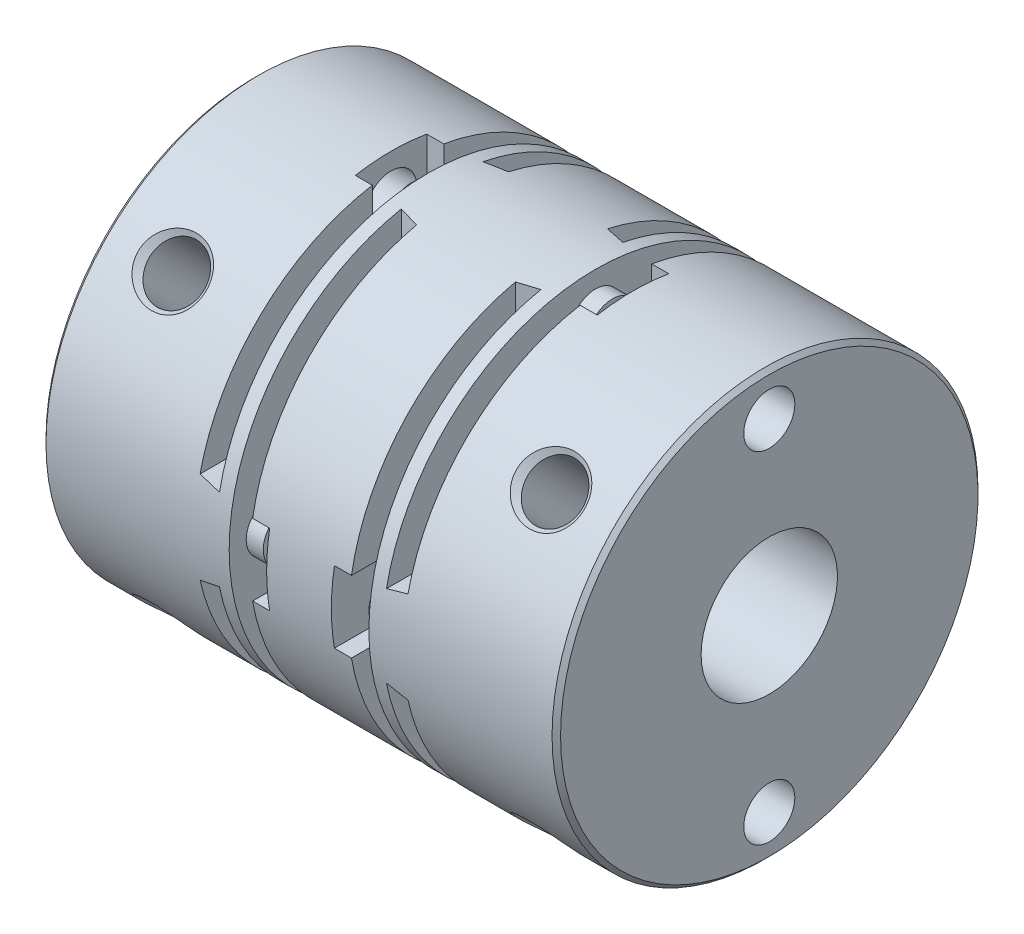
SolidWorks part; units mm, degrees
material "6061 合金"
ref_plane "前视基准面" through (0, 0, 0) normal (0, 0, 1) x (1, 0, 0)
ref_plane "上视基准面" through (0, 0, 0) normal (0, 1, 0) x (1, 0, 0)
ref_plane "右视基准面" through (0, 0, 0) normal (1, 0, 0) x (0, 0, -1)
sketch "草图1" plane through (0, 0, 0) normal (0, 0, 1) x (1, 0, 0)
  line L0 (0, 4) -> (9, 4)
  line L1 (9, 4) -> (9, 7.5)
  line L2 (9, 7.5) -> (10.2, 7.5)
  line L3 (10.2, 7.5) -> (10.2, 6)
  line L4 (10.2, 6) -> (11, 6)
  line L5 (11, 6) -> (11, 7.5)
  line L6 (11, 7.5) -> (12.2, 7.5)
  line L7 (12.2, 7.5) -> (12.2, 5.2)
  line L8 (12.2, 5.2) -> (18, 5.2)
  line L9 (18, 5.2) -> (18, 7.5)
  line L10 (18, 7.5) -> (19.2, 7.5)
  line L11 (19.2, 7.5) -> (19.2, 6)
  line L12 (19.2, 6) -> (20, 6)
  line L13 (20, 6) -> (20, 7.5)
  line L14 (20, 7.5) -> (21.2, 7.5)
  line L15 (21.2, 7.5) -> (21.2, 4)
  line L16 (21.2, 4) -> (30.2, 4)
  line L17 (30.2, 4) -> (30.2, 12.25)
  line L18 (30.2, 12.25) -> (29.95, 12.5)
  line L19 (29.95, 12.5) -> (0.25, 12.5)
  line L20 (0.25, 12.5) -> (0, 12.25)
  line L21 (0, 12.25) -> (0, 4)
  line L22 (30.2, 0) -> (0, 0) construction
revolve "旋转1" add sketch "草图1" angle 360 about L22 reverse direction yes
ref_plane "基准面1" through (4, 0, 0) normal (1, 0, 0) x (0, 0, -1)
sketch "草图2" plane through (4, 0, 0) normal (1, 0, 0) x (0, 0, -1)
  line L0 (-8.8388, 8.8388) -> (-7.4246, 10.253)
  line L1 (-7.4246, 10.253) -> (-7.4246, 9.7171)
  line L2 (-7.4246, 9.7171) -> (1.1462, 1.1462)
  line L3 (1.1462, 1.1462) -> (0, 0)
  line L4 (0, 0) -> (-8.8388, 8.8388)
  line L5 (0, 0) -> (-8.8388, 8.8388) construction
revolve "切除-旋转1" cut sketch "草图2" angle 360 about L5 reverse direction yes
cosmetic thread "装饰螺纹线1" parameters "D1"=8.5, "D2"=4
sketch "草图3" plane through (4, 0, 0) normal (1, 0, 0) x (0, 0, -1)
  line L0 (-8.8388, -8.8388) -> (-10.253, -7.4246)
  line L1 (-10.253, -7.4246) -> (-9.7171, -7.4246)
  line L2 (-9.7171, -7.4246) -> (-1.1462, 1.1462)
  line L3 (-1.1462, 1.1462) -> (0, 0)
  line L4 (0, 0) -> (-8.8388, -8.8388)
  line L5 (0, 0) -> (-8.8388, -8.8388) construction
revolve "切除-旋转2" cut sketch "草图3" angle 360 about L5 reverse direction yes
cosmetic thread "装饰螺纹线2" parameters "D1"=8.5, "D2"=4
ref_plane "基准面2" through (26.2, 0, 0) normal (1, 0, 0) x (0, 0, -1)
sketch "草图4" plane through (26.2, 0, 0) normal (1, 0, 0) x (0, 0, -1)
  line L0 (-8.8388, 8.8388) -> (-7.4246, 10.253)
  line L1 (-7.4246, 10.253) -> (-7.4246, 9.7171)
  line L2 (-7.4246, 9.7171) -> (1.1462, 1.1462)
  line L3 (1.1462, 1.1462) -> (0, 0)
  line L4 (0, 0) -> (-8.8388, 8.8388)
  line L5 (0, 0) -> (-8.8388, 8.8388) construction
revolve "切除-旋转3" cut sketch "草图4" angle 360 about L5 reverse direction yes
cosmetic thread "装饰螺纹线3" parameters "D1"=8.5, "D2"=4
sketch "草图5" plane through (26.2, 0, 0) normal (1, 0, 0) x (0, 0, -1)
  line L0 (-8.8388, -8.8388) -> (-10.253, -7.4246)
  line L1 (-10.253, -7.4246) -> (-9.7171, -7.4246)
  line L2 (-9.7171, -7.4246) -> (-1.1462, 1.1462)
  line L3 (-1.1462, 1.1462) -> (0, 0)
  line L4 (0, 0) -> (-8.8388, -8.8388)
  line L5 (0, 0) -> (-8.8388, -8.8388) construction
revolve "切除-旋转4" cut sketch "草图5" angle 360 about L5 reverse direction yes
cosmetic thread "装饰螺纹线4" parameters "D1"=8.5, "D2"=4
sketch "草图6" plane through (0, 0, 0) normal (0, 0, 1) x (1, 0, 0)
  line L0 (9, 13) -> (9, 2.7)
  line L1 (9, 2.7) -> (10.2, 2.4)
  line L2 (10.2, 2.4) -> (10.2, 12.5)
  line L3 (10.2, 12.5) -> (20, 12.5)
  line L4 (20, 12.5) -> (20, 2.4)
  line L5 (20, 2.4) -> (21.2, 2.7)
  line L6 (21.2, 2.7) -> (21.2, 13)
  line L7 (21.2, 13) -> (9, 13)
extrude "切除-拉伸1" cut sketch "草图6" along normal blind 12.5 and the other way blind 12.5
sketch "草图7" plane through (0, 0, 0) normal (0, 0, 1) x (1, 0, 0)
  line L0 (9, -13) -> (21.2, -13)
  line L1 (21.2, -13) -> (21.2, -2.7)
  line L2 (21.2, -2.7) -> (20, -2.4)
  line L3 (20, -2.4) -> (20, -12.5)
  line L4 (20, -12.5) -> (10.2, -12.5)
  line L5 (10.2, -12.5) -> (10.2, -2.4)
  line L6 (10.2, -2.4) -> (9, -2.7)
  line L7 (9, -2.7) -> (9, -13)
extrude "切除-拉伸2" cut sketch "草图7" along normal blind 12.5 and the other way blind 12.5
sketch "草图8" plane through (0, 0, 0) normal (0, 1, 0) x (1, 0, 0)
  line L0 (11, 13) -> (11, 2.4)
  line L1 (11, 2.4) -> (12.2, 2.7)
  line L2 (12.2, 2.7) -> (12.2, 12.5)
  line L3 (12.2, 12.5) -> (18, 12.5)
  line L4 (18, 12.5) -> (18, 2.7)
  line L5 (18, 2.7) -> (19.2, 2.4)
  line L6 (19.2, 2.4) -> (19.2, 13)
  line L7 (19.2, 13) -> (11, 13)
extrude "切除-拉伸3" cut sketch "草图8" along normal blind 12.5 and the other way blind 12.5
sketch "草图9" plane through (0, 0, 0) normal (0, 1, 0) x (1, 0, 0)
  line L0 (11, -13) -> (19.2, -13)
  line L1 (19.2, -13) -> (19.2, -2.4)
  line L2 (19.2, -2.4) -> (18, -2.7)
  line L3 (18, -2.7) -> (18, -12.5)
  line L4 (18, -12.5) -> (12.2, -12.5)
  line L5 (12.2, -12.5) -> (12.2, -2.7)
  line L6 (12.2, -2.7) -> (11, -2.4)
  line L7 (11, -2.4) -> (11, -13)
extrude "切除-拉伸4" cut sketch "草图9" along normal blind 12.5 and the other way blind 12.5
ref_plane "基准面3" through (18, 0, 0) normal (1, 0, 0) x (0, 0, -1)
sketch "草图10" plane through (18, 0, 0) normal (1, 0, 0) x (0, 0, -1)
  line L0 (-12.5, -2.1) -> (-10, -2.1)
  line L1 (-10, 2.1) -> (-12.5, 2.1)
  line L2 (-12.5, 2.1) -> (-12.5, -2.1)
  arc A0 (-10, -2.1) -> (-10, 2.1) centre (-10, 0) ccw
extrude "切除-拉伸5" cut sketch "草图10" against normal blind 1
sketch "草图11" plane through (18, 0, 0) normal (1, 0, 0) x (0, 0, -1)
  line L0 (10, -2.1) -> (12.5, -2.1)
  line L1 (12.5, -2.1) -> (12.5, 2.1)
  line L2 (12.5, 2.1) -> (10, 2.1)
  arc A0 (10, 2.1) -> (10, -2.1) centre (10, 0) ccw
extrude "切除-拉伸6" cut sketch "草图11" against normal blind 1
ref_plane "基准面4" through (12.2, 0, 0) normal (1, 0, 0) x (0, 0, -1)
sketch "草图12" plane through (12.2, 0, 0) normal (1, 0, 0) x (0, 0, -1)
  line L0 (-12.5, -2.1) -> (-10, -2.1)
  line L1 (-10, 2.1) -> (-12.5, 2.1)
  line L2 (-12.5, 2.1) -> (-12.5, -2.1)
  arc A0 (-10, -2.1) -> (-10, 2.1) centre (-10, 0) ccw
extrude "切除-拉伸7" cut sketch "草图12" along normal blind 1
sketch "草图13" plane through (12.2, 0, 0) normal (1, 0, 0) x (0, 0, -1)
  line L0 (10, -2.1) -> (12.5, -2.1)
  line L1 (12.5, -2.1) -> (12.5, 2.1)
  line L2 (12.5, 2.1) -> (10, 2.1)
  arc A0 (10, 2.1) -> (10, -2.1) centre (10, 0) ccw
extrude "切除-拉伸8" cut sketch "草图13" along normal blind 1
ref_plane "基准面5" through (9, 0, 0) normal (1, 0, 0) x (0, 0, -1)
sketch "草图14" plane through (9, 0, 0) normal (1, 0, 0) x (0, 0, -1)
  line L0 (2.1, 10) -> (2.1, 12.5)
  line L1 (2.1, 12.5) -> (-2.1, 12.5)
  line L2 (-2.1, 12.5) -> (-2.1, 10)
  arc A0 (-2.1, 10) -> (2.1, 10) centre (0, 10) ccw
extrude "切除-拉伸9" cut sketch "草图14" against normal blind 1
sketch "草图15" plane through (9, 0, 0) normal (1, 0, 0) x (0, 0, -1)
  line L0 (-2.1, -10) -> (-2.1, -12.5)
  line L1 (-2.1, -12.5) -> (2.1, -12.5)
  line L2 (2.1, -12.5) -> (2.1, -10)
  arc A0 (2.1, -10) -> (-2.1, -10) centre (0, -10) ccw
extrude "切除-拉伸10" cut sketch "草图15" against normal blind 1
ref_plane "基准面6" through (21.2, 0, 0) normal (1, 0, 0) x (0, 0, -1)
sketch "草图16" plane through (21.2, 0, 0) normal (1, 0, 0) x (0, 0, -1)
  line L0 (2.1, 10) -> (2.1, 12.5)
  line L1 (2.1, 12.5) -> (-2.1, 12.5)
  line L2 (-2.1, 12.5) -> (-2.1, 10)
  arc A0 (-2.1, 10) -> (2.1, 10) centre (0, 10) ccw
extrude "切除-拉伸11" cut sketch "草图16" along normal blind 1
sketch "草图17" plane through (21.2, 0, 0) normal (1, 0, 0) x (0, 0, -1)
  line L0 (-2.1, -10) -> (-2.1, -12.5)
  line L1 (-2.1, -12.5) -> (2.1, -12.5)
  line L2 (2.1, -12.5) -> (2.1, -10)
  arc A0 (2.1, -10) -> (-2.1, -10) centre (0, -10) ccw
extrude "切除-拉伸12" cut sketch "草图17" along normal blind 1
ref_plane "基准面7" through (11, 0, 0) normal (1, 0, 0) x (0, 0, -1)
sketch "草图18" plane through (11, 0, 0) normal (1, 0, 0) x (0, 0, -1)
  circle A0 centre (-10, 0) radius 1.5
extrude "凸台-拉伸1" add sketch "草图18" along normal blind 1
sketch "草图19" plane through (11, 0, 0) normal (1, 0, 0) x (0, 0, -1)
  circle A0 centre (10, 0) radius 1.5
extrude "凸台-拉伸2" add sketch "草图19" along normal blind 1
ref_plane "基准面8" through (10.2, 0, 0) normal (1, 0, 0) x (0, 0, -1)
sketch "草图20" plane through (10.2, 0, 0) normal (1, 0, 0) x (0, 0, -1)
  circle A0 centre (0, 10) radius 1.5
extrude "凸台-拉伸3" add sketch "草图20" against normal blind 1
sketch "草图21" plane through (10.2, 0, 0) normal (1, 0, 0) x (0, 0, -1)
  circle A0 centre (0, -10) radius 1.5
extrude "凸台-拉伸4" add sketch "草图21" against normal blind 1
ref_plane "基准面9" through (19.2, 0, 0) normal (1, 0, 0) x (0, 0, -1)
sketch "草图22" plane through (19.2, 0, 0) normal (1, 0, 0) x (0, 0, -1)
  circle A0 centre (-10, 0) radius 1.5
extrude "凸台-拉伸5" add sketch "草图22" against normal blind 1
sketch "草图23" plane through (19.2, 0, 0) normal (1, 0, 0) x (0, 0, -1)
  circle A0 centre (10, 0) radius 1.5
extrude "凸台-拉伸6" add sketch "草图23" against normal blind 1
ref_plane "基准面10" through (20, 0, 0) normal (1, 0, 0) x (0, 0, -1)
sketch "草图24" plane through (20, 0, 0) normal (1, 0, 0) x (0, 0, -1)
  circle A0 centre (0, 10) radius 1.5
extrude "凸台-拉伸7" add sketch "草图24" along normal blind 1
sketch "草图25" plane through (20, 0, 0) normal (1, 0, 0) x (0, 0, -1)
  circle A0 centre (0, -10) radius 1.5
extrude "凸台-拉伸8" add sketch "草图25" along normal blind 1
hole_wizard "孔1" positions "草图27" profile "草图26" legacy
sketch "草图27" plane through (0, 0, 0) normal (-1, 0, 0) x (0, 0, 1)
  point P0 (0, 10)
sketch "草图26" plane through (0, 10, 0) normal (0, 1, 0) x (0, 0, 1)
  line L0 (0, 0) -> (0, 9)
  line L1 (0, 9) -> (1.5, 9)
  line L2 (1.5, 9) -> (1.5, 0)
  line L3 (1.5, 0) -> (0, 0)
  line L4 (0, 110) -> (0, -10) construction
  dimension "直径" = 3
  dimension "深度" = 9
hole_wizard "孔2" positions "草图29" profile "草图28" legacy
sketch "草图29" plane through (0, 0, 0) normal (-1, 0, 0) x (0, 0, 1)
  point P0 (0, -10)
sketch "草图28" plane through (0, -10, 0) normal (0, 1, 0) x (0, 0, 1)
  line L0 (0, 0) -> (0, 9)
  line L1 (0, 9) -> (1.5, 9)
  line L2 (1.5, 9) -> (1.5, 0)
  line L3 (1.5, 0) -> (0, 0)
  line L4 (0, 110) -> (0, -10) construction
  dimension "直径" = 3
  dimension "深度" = 9
ref_plane "基准面11" through (30.2, 0, 0) normal (1, 0, 0) x (0, 0, -1)
hole_wizard "孔3" positions "草图31" profile "草图30" legacy
sketch "草图31" plane through (30.2, 0, 0) normal (1, 0, 0) x (0, 0, -1)
  point P0 (0, 10)
sketch "草图30" plane through (30.2, 10, 0) normal (0, 1, 0) x (0, 0, -1)
  line L0 (0, 0) -> (0, 9)
  line L1 (0, 9) -> (1.5, 9)
  line L2 (1.5, 9) -> (1.5, 0)
  line L3 (1.5, 0) -> (0, 0)
  line L4 (0, 110) -> (0, -10) construction
  dimension "直径" = 3
  dimension "深度" = 9
hole_wizard "孔4" positions "草图33" profile "草图32" legacy
sketch "草图33" plane through (30.2, 0, 0) normal (1, 0, 0) x (0, 0, -1)
  point P0 (0, -10)
sketch "草图32" plane through (30.2, -10, 0) normal (0, 1, 0) x (0, 0, -1)
  line L0 (0, 0) -> (0, 9)
  line L1 (0, 9) -> (1.5, 9)
  line L2 (1.5, 9) -> (1.5, 0)
  line L3 (1.5, 0) -> (0, 0)
  line L4 (0, 110) -> (0, -10) construction
  dimension "直径" = 3
  dimension "深度" = 9
ref_plane "基准面12" through (0, 0, 0) normal (0, -0.7071, 0.7071) x (1, 0, 0)
ref_plane "基准面13" through (0, -8.8388, 8.8388) normal (0, -0.7071, 0.7071) x (1, 0, 0)
ref_plane "基准面14" through (0, 0, 0) normal (0, 0.7071, 0.7071) x (1, 0, 0)
ref_plane "基准面15" through (0, 8.8388, 8.8388) normal (0, 0.7071, 0.7071) x (1, 0, 0)
ref_plane "to_screw1 XY" through (0, -8.8388, 8.8388) normal (0, -0.7071, 0.7071) x (1, 0, 0)
ref_plane "to_screw1 XZ" through (0, 0, 0) normal (0, -0.7071, -0.7071) x (-1, 0, 0)
ref_plane "to_screw1 YZ" through (4, 0, 0) normal (1, 0, 0) x (0, 0, -1)
ref_axis "to_screw1 X" through (-80.9, -8.8388, 8.8388) along (1, 0, 0)
ref_axis "to_screw1 Y" through (4, -44.1942, -26.5165) along (0, 0.7071, 0.7071)
ref_axis "to_screw1 Z" through (4, -50, 50) along (0, 0.7071, -0.7071)
sketch3d "to_screw1"
  point P0 (4, -8.8388, 8.8388)
ref_plane "to_screw2 XY" through (0, -8.8388, 8.8388) normal (0, -0.7071, 0.7071) x (1, 0, 0)
ref_plane "to_screw2 XZ" through (0, 0, 0) normal (0, -0.7071, -0.7071) x (-1, 0, 0)
ref_plane "to_screw2 YZ" through (26.2, 0, 0) normal (1, 0, 0) x (0, 0, -1)
ref_axis "to_screw2 X" through (-80.9, -8.8388, 8.8388) along (1, 0, 0)
ref_axis "to_screw2 Y" through (26.2, -44.1942, -26.5165) along (0, 0.7071, 0.7071)
ref_axis "to_screw2 Z" through (26.2, -50, 50) along (0, 0.7071, -0.7071)
sketch3d "to_screw2"
  point P0 (26.2, -8.8388, 8.8388)
ref_plane "to_screw3 XY" through (0, 8.8388, 8.8388) normal (0, 0.7071, 0.7071) x (1, 0, 0)
ref_plane "to_screw3 XZ" through (0, 0, 0) normal (0, -0.7071, 0.7071) x (-1, 0, 0)
ref_plane "to_screw3 YZ" through (4, 0, 0) normal (1, 0, 0) x (0, 0, -1)
ref_axis "to_screw3 X" through (-80.9, 8.8388, 8.8388) along (1, 0, 0)
ref_axis "to_screw3 Y" through (4, -26.5165, 44.1942) along (0, 0.7071, -0.7071)
ref_axis "to_screw3 Z" through (4, 50, 50) along (0, -0.7071, -0.7071)
sketch3d "to_screw3"
  point P0 (4, 8.8388, 8.8388)
ref_plane "to_screw4 XY" through (0, 8.8388, 8.8388) normal (0, 0.7071, 0.7071) x (1, 0, 0)
ref_plane "to_screw4 XZ" through (0, 0, 0) normal (0, -0.7071, 0.7071) x (-1, 0, 0)
ref_plane "to_screw4 YZ" through (26.2, 0, 0) normal (1, 0, 0) x (0, 0, -1)
ref_axis "to_screw4 X" through (-80.9, 8.8388, 8.8388) along (1, 0, 0)
ref_axis "to_screw4 Y" through (26.2, -26.5165, 44.1942) along (0, 0.7071, -0.7071)
ref_axis "to_screw4 Z" through (26.2, 50, 50) along (0, -0.7071, -0.7071)
sketch3d "to_screw4"
  point P0 (26.2, 8.8388, 8.8388)
